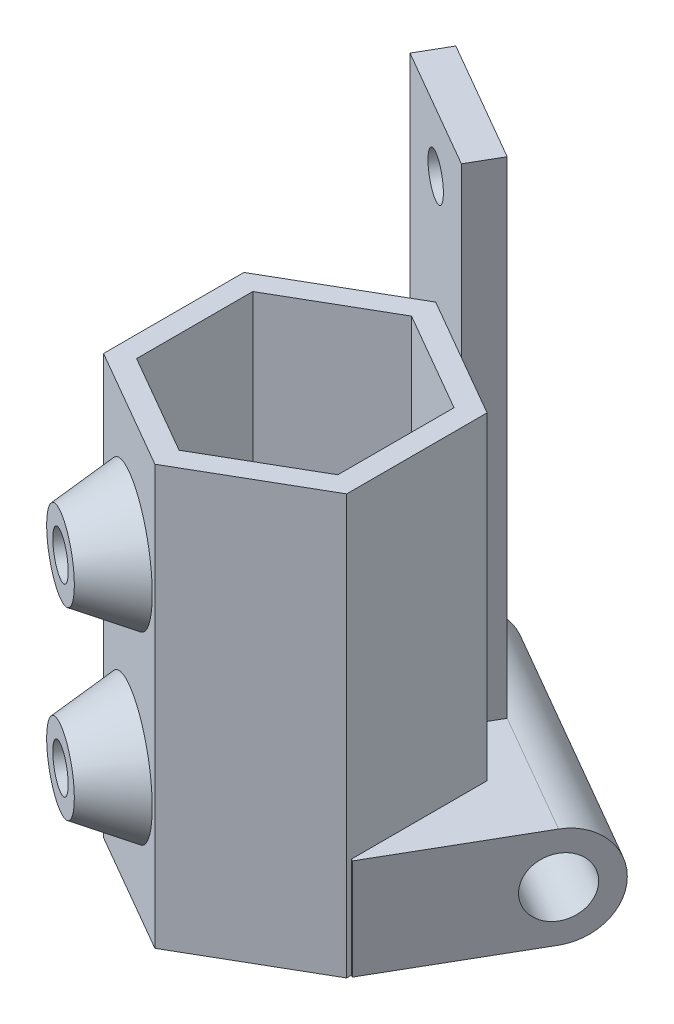
SolidWorks part; units mm, degrees
ref_plane "Plano frontal" through (0, 0, 0) normal (0, 0, 1) x (1, 0, 0)
ref_plane "Plano superior" through (0, 0, 0) normal (0, 1, 0) x (1, 0, 0)
ref_plane "Plano direito" through (0, 0, 0) normal (1, 0, 0) x (0, 0, -1)
sketch "Esboço1" plane through (0, 0, 0) normal (0, 1, 0) x (1, 0, 0)
  line L0 (0, 16.3256) -> (0, -14.1372) construction
  line L2 (7.25, 4.1858) -> (0, 8.3716)
  line L3 (0, 8.3716) -> (-7.25, 4.1858)
  line L4 (-7.25, 4.1858) -> (-7.25, -4.1858)
  line L5 (-7.25, -4.1858) -> (0, -8.3716)
  line L6 (0, -8.3716) -> (7.25, -4.1858)
  line L7 (7.25, -4.1858) -> (7.25, 4.1858)
  circle A0 centre (0, 0) radius 7.25 construction
  dimension "D1" = 14.5
extrude "Ressalto-extrusão1" add sketch "Esboço1" along normal blind 25
sketch "Esboço3" plane through (-3.625, 0, 6.2787) normal (-0.5, 0, 0.866) x (0.866, 0, 0.5)
  line L0 (0, -3.2486) -> (0, 27.6023) construction
  line L1 (-4.1858, 0) -> (4.1858, 0) construction
  line L2 (-11.1774, 12.5) -> (14.0862, 12.5) construction
  circle A0 centre (0, 7) radius 2.25
  circle A1 centre (0, 18) radius 2.25
  dimension "D1" = 4.5
  dimension "D2" = 7
extrude "Ressalto-extrusão2" add sketch "Esboço3" along normal blind 3
ref_plane "Plano1" through (0, 18, 0) normal (0, 1, 0) x (1, 0, 0)
sketch "Esboço4" plane through (0, 18, 0) normal (0, 1, 0) x (1, 0, 0)
  line L0 (-7.0736, -7.7518) -> (-6.8726, -4.4037)
  line L1 (-7.25, -4.1858) -> (0, -8.3716) construction
  line L2 (-6.8726, -4.4037) -> (-5.5736, -5.1537)
  line L3 (-5.5736, -5.1537) -> (-7.0736, -7.7518)
  line L4 (-2.5653, -4.4432) -> (-6.112, -10.5863) construction
  dimension "D1" = 1.5
revolve "Revolução1" add sketch "Esboço4" angle 360 about L4
ref_plane "Plano2" through (0, 7, 0) normal (0, -1, 0) x (-1, 0, 0)
sketch "Esboço5" plane through (0, 7, 0) normal (0, -1, 0) x (-1, 0, 0)
  line L0 (7.0736, -7.7518) -> (5.5736, -5.1537)
  line L1 (5.5736, -5.1537) -> (6.8726, -4.4037)
  line L2 (7.25, -4.1858) -> (0, -8.3716) construction
  line L3 (6.8726, -4.4037) -> (7.0736, -7.7518)
  line L4 (5.5736, -9.6537) -> (1.9867, -3.4411) construction
  dimension "D1" = 1.5
revolve "Revolução2" add sketch "Esboço5" angle 360 about L4
sketch "Esboço6" plane through (-5.125, 0, 8.8768) normal (-0.5, 0, 0.866) x (0.866, 0, 0.5)
  line L0 (0, 23.2309) -> (0, 1.0123) construction
  line L1 (4.2911, 18) -> (-4.8168, 18) construction
  line L2 (7.975, 18) -> (-7.975, 18) construction
  line L3 (4.1858, 12.5) -> (-4.1858, 12.5) construction
  line L4 (4.1858, 25) -> (4.1858, 0) construction
  line L5 (-4.1858, 25) -> (-4.1858, 0) construction
  circle A0 centre (0, 18) radius 1.25
  circle A1 centre (0, 7) radius 1.25
  dimension "D1" = 2.5
extrude "Corte-extrusão2" cut sketch "Esboço6" against normal blind 10
sketch "Esboço8" plane through (3.625, 0, -6.2787) normal (0.5, 0, -0.866) x (-0.866, 0, -0.5)
  line L0 (0, -2.0151) -> (0, 13.6082) construction
  line L1 (-8.3716, 25) -> (-8.3716, 0) construction
  line L2 (-8.3716, 6) -> (8.3716, 6)
  line L3 (-8.3716, 6) -> (-8.3716, 0)
  line L4 (-8.3716, 0) -> (8.3716, 0)
  line L5 (8.3716, 6) -> (8.3716, 0)
  dimension "D1" = 6
extrude "Ressalto-extrusão3" add sketch "Esboço8" along normal blind 5 and the other way blind 7
sketch "Esboço2" plane through (0, 25, 0) normal (0, 1, 0) x (1, 0, 0)
  line L1 (0, 6.9282) -> (-6, 3.4641)
  line L2 (-6, 3.4641) -> (-6, -3.4641)
  line L3 (-6, -3.4641) -> (0, -6.9282)
  line L4 (0, -6.9282) -> (6, -3.4641)
  line L5 (6, -3.4641) -> (6, 3.4641)
  line L6 (6, 3.4641) -> (0, 6.9282)
  circle A0 centre (0, 0) radius 6 construction
extrude "Corte-extrusão1" cut sketch "Esboço2" against normal through all
fillet "Filete2" radius 3 2 edges at (6.125, 0, -10.6088) (6.125, 6, -10.6088)
sketch "Esboço10" plane through (-7.25, 0, -4.1858) normal (-0.866, 0, -0.5) x (-0.5, 0, 0.866)
  line L0 (-0.25, 3) -> (-15.2161, 3) construction
  line L1 (-0.25, 0) -> (-0.25, 6) construction
  circle A0 centre (-9.25, 3) radius 1.75
  dimension "D1" = 3.5
  dimension "D2" = 3
extrude "Corte-extrusão3" cut sketch "Esboço10" against normal through all
sketch "Esboço11" plane through (0, 6, 0) normal (0, 1, 0) x (1, 0, 0)
  line L0 (-3, -5.1962) -> (8.0117, 13.8767) construction
  line L1 (-6, -3.4641) -> (0, -6.9282) construction
  line L2 (-2.625, 12.1965) -> (4.625, 8.0107)
  line L3 (11.875, 3.8249) -> (-2.625, 12.1965) construction
  line L4 (4.625, 8.0107) -> (3.625, 6.2787)
  line L5 (7.25, 4.1858) -> (0, 8.3716) construction
  line L6 (3.625, 6.2787) -> (-3.625, 10.4645)
  line L7 (-7.125, 4.4023) -> (-2.625, 12.1965) construction
  line L8 (-3.625, 10.4645) -> (-2.625, 12.1965)
extrude "Ressalto-extrusão4" add sketch "Esboço11" along normal blind 29
sketch "Esboço12" plane through (3.625, 0, -6.2787) normal (-0.5, 0, 0.866) x (0.866, 0, 0.5)
  line L0 (-4.1858, 35) -> (-4.1858, -2.367) construction
  line L1 (-8.3716, 35) -> (0, 35) construction
  circle A0 centre (-4.1858, 31.5) radius 1.25
  dimension "D1" = 2.5
  dimension "D2" = 3.5
extrude "Corte-extrusão4" cut sketch "Esboço12" against normal through all
